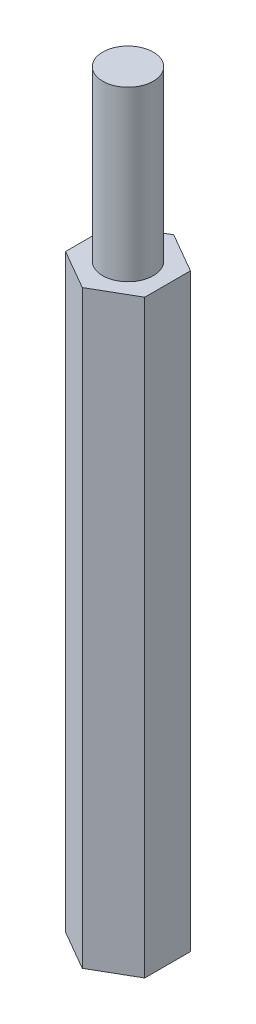
SolidWorks part; units mm, degrees
other "Markup1"
sketch "Sketch6" plane through (2.35, 45, 2.7135) normal (0.424, 0.6635, 0.6165) x (0.8139, 0.0195, -0.5807)
sketch "Sketch7" plane through (2.35, 45, 2.7135) normal (0.424, 0.6635, 0.6165) x (0.8139, 0.0195, -0.5807)
material "Nickel"
ref_plane "Front Plane" through (0, 0, 0) normal (0, 0, 1) x (1, 0, 0)
ref_plane "Top Plane" through (0, 0, 0) normal (0, 1, 0) x (1, 0, 0)
ref_plane "Right Plane" through (0, 0, 0) normal (1, 0, 0) x (0, 0, -1)
sketch "Sketch1" plane through (0, 0, 0) normal (0, 1, 0) x (1, 0, 0)
  line L1 (0, 2.7135) -> (-2.35, 1.3568)
  line L2 (-2.35, 1.3568) -> (-2.35, -1.3568)
  line L3 (-2.35, -1.3568) -> (0, -2.7135)
  line L4 (0, -2.7135) -> (2.35, -1.3568)
  line L5 (2.35, -1.3568) -> (2.35, 1.3568)
  line L6 (2.35, 1.3568) -> (0, 2.7135)
  circle A0 centre (0, 0) radius 2.35 construction
  dimension "D1" = 4.7
extrude "Boss-Extrude1" add sketch "Sketch1" along normal blind 35
sketch "Sketch2" plane through (0, 35, 0) normal (0, 1, 0) x (1, 0, 0)
  circle A0 centre (0, 0) radius 1.5
  dimension "D1" = 3
extrude "Boss-Extrude2" add sketch "Sketch2" along normal blind 10
sketch "Sketch5" plane through (0, 0, 0) normal (0, -1, 0) x (1, 0, 0)
  circle A0 centre (0, 0) radius 1.5
  dimension "D1" = 3
extrude "Cut-Extrude1" cut sketch "Sketch5" against normal blind 10
